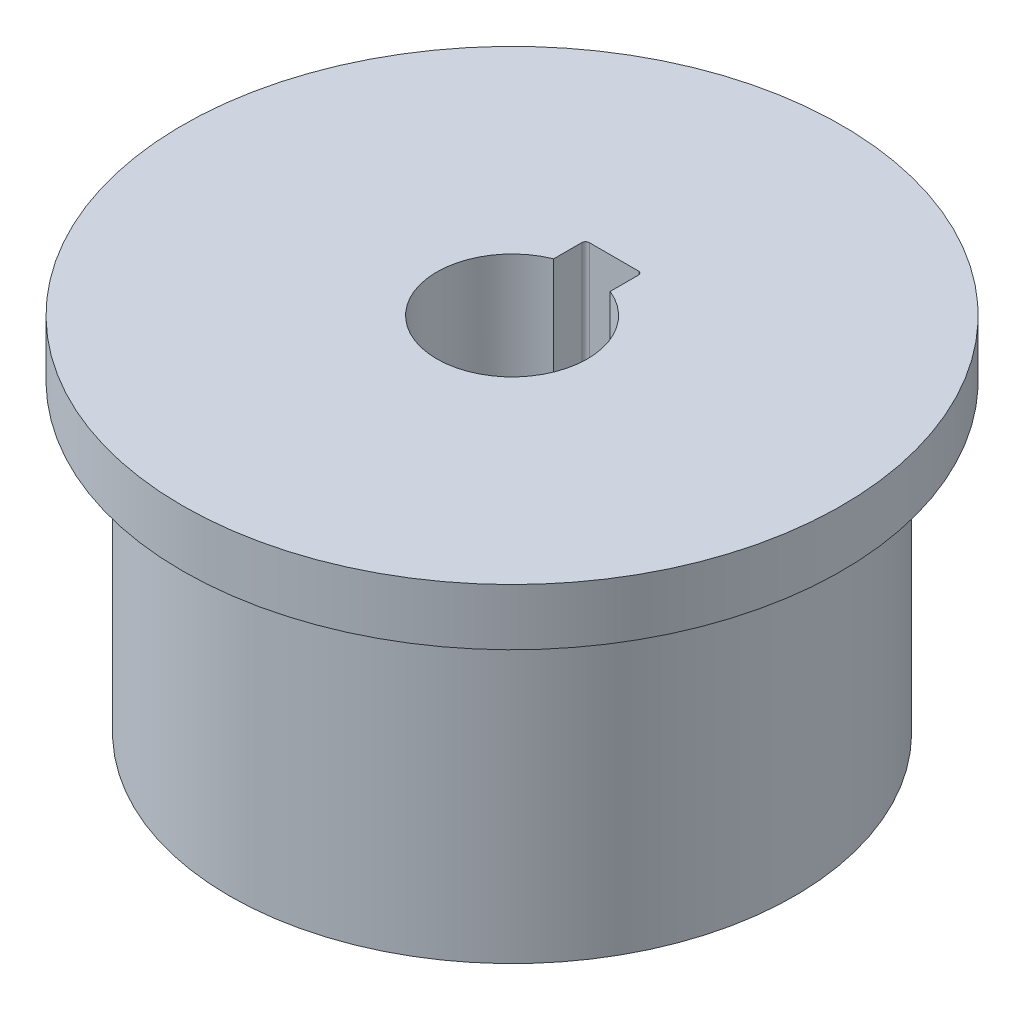
SolidWorks part; units mm, degrees
ref_plane "Plan de face" through (0, 0, 0) normal (0, 0, 1) x (1, 0, 0)
ref_plane "Plan de dessus" through (0, 0, 0) normal (0, 1, 0) x (1, 0, 0)
ref_plane "Plan de droite" through (0, 0, 0) normal (1, 0, 0) x (0, 0, -1)
sketch "Sketch1" plane through (0, 0, 0) normal (0, 0, 1) x (1, 0, 0)
  line L0 (0, 12.7093) -> (0, -8.2237) construction
  line L1 (4, 19.2) -> (17.5, 19.2)
  line L2 (17.5, 19.2) -> (17.5, 16.2)
  line L3 (17.5, 16.2) -> (15, 16.2)
  line L4 (15, 16.2) -> (15, 0)
  line L14 (4, -4) -> (4, 19.2)
  line L15 (4, -4) -> (5, -4)
  line L16 (8, -1) -> (8, 16.2)
  line L17 (15, 0) -> (12, 0)
  line L18 (12, 0) -> (12, 16.2)
  line L19 (12, 16.2) -> (8, 16.2)
  line L20 (5, -4) -> (8, -1)
  dimension "D1" = 16.2
  dimension "D2" = 3
  dimension "D3" = 17.5
  dimension "D4" = 15
  dimension "D5" = 4
  dimension "D6" = 3
  dimension "D7" = 1
  dimension "D8" = 45
  dimension "D9" = 8
  dimension "D10" = 4
revolve "Revolve1" add sketch "Sketch1" angle 360 about L0
sketch "Esquisse1" plane through (0, 19.2, 0) normal (0, 1, 0) x (1, 0, 0)
  line L0 (-1.5, 3.7081) -> (-1.5, 5.4)
  line L1 (-1.5, 5.4) -> (1.5, 5.4)
  line L2 (1.5, 5.4) -> (1.5, 3.7081)
  circle A1 centre (0, 0) radius 4 construction
  arc A2 (-1.5, 3.7081) -> (1.5, 3.7081) centre (0, 0) cw
  point P2 (-1.5, 3.7081)
  point P4 (0, 5.4)
  circle M2 centre (0, 0) radius 4
  dimension "D1" = 1.4
  dimension "D2" = 3
extrude "Enlèv. mat.-Extru.1" cut sketch "Esquisse1" against normal blind 15 contours L2 L1 L0 M2 region at (0, 19.2, -4.6496)
fillet "Congé1" radius 0.2 2 edges at (1.5, 11.7, -5.4) (-1.5, 11.7, -5.4)
